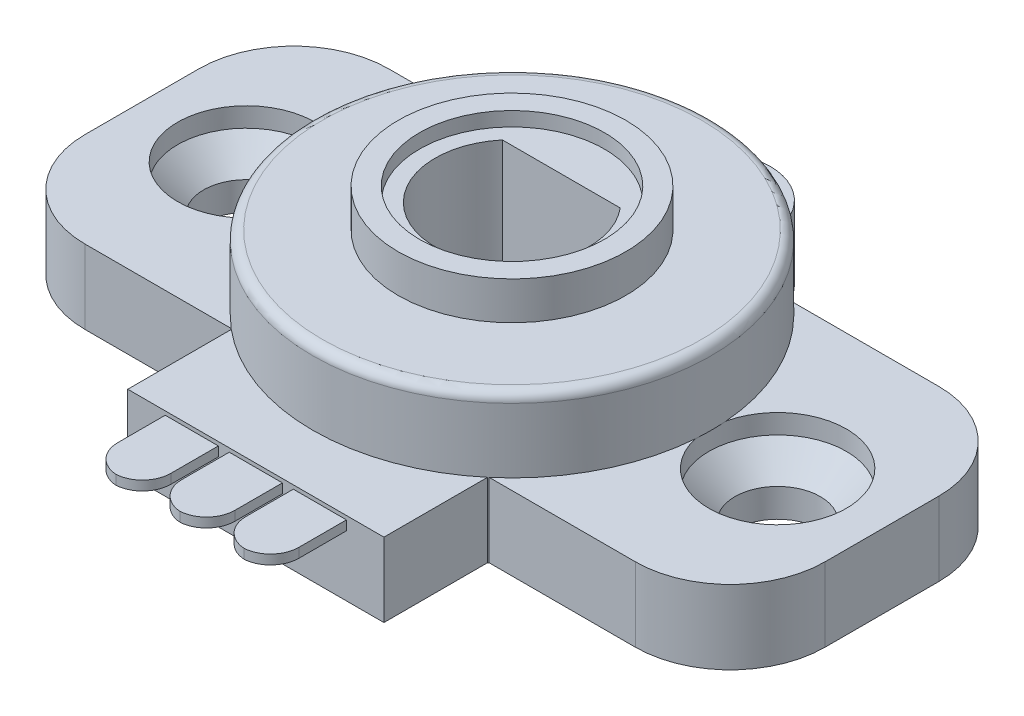
SolidWorks part; units mm, degrees
ref_plane "Front Plane" through (0, 0, 0) normal (0, 0, 1) x (1, 0, 0)
ref_plane "Top Plane" through (0, 0, 0) normal (0, 1, 0) x (1, 0, 0)
ref_plane "Right Plane" through (0, 0, 0) normal (1, 0, 0) x (0, 0, -1)
sketch "Sketch2" plane through (0, 0, 0) normal (0, 1, 0) x (1, 0, 0)
  line L0 (-1000, 0) -> (49000, 0) construction
  line L1 (-14.5, -8) -> (14.5, -8)
  line L2 (-19.5, -3) -> (-19.5, 3)
  line L3 (-14.5, 8) -> (14.5, 8)
  line L4 (19.5, -3) -> (19.5, 3)
  line L8 (-6.75, -8) -> (6.75, -8)
  line L9 (-6.75, -8) -> (-6.75, -13.5)
  line L10 (-6.75, -13.5) -> (6.75, -13.5)
  line L11 (6.75, -8) -> (6.75, -13.5)
  arc A0 (14.5, 8) -> (19.5, 3) centre (14.5, 3) cw
  arc A1 (14.5, -8) -> (19.5, -3) centre (14.5, -3) ccw
  arc A2 (-14.5, -8) -> (-19.5, -3) centre (-14.5, -3) cw
  arc A3 (-19.5, 3) -> (-14.5, 8) centre (-14.5, 3) cw
  circle A4 centre (0, 0) radius 10.5
  circle A5 centre (0, 10.5) radius 3.1
  point P0 (0, 0)
  point P1 (0, -8)
  point P2 (-19.5, 0)
  point P24 (0, -13.5)
  dimension "D3" = 5
  dimension "D4" = 21
  dimension "D5" = 6.2
  dimension "D6" = 13.6
  dimension "D1" = 39
  dimension "D2" = 16
  dimension "D7" = 13.5
  dimension "D8" = 13.5
extrude "Boss-Extrude1" add sketch "Sketch2" along normal blind 3.9 contours A4 A5 | L2 L0 A4 L3 A3 | L0 L2 A2 L1 A4 | A4 L0 L3 A5 | L0 A4 L1 | L9 A4 L11 L1 | A4 L9 L10 L11 | A4 L0 L4 A0 L3 | L0 A4 L1 A1 L4 | L3 A5 | A5 A4 L3 | L3 A5 A4 | A5 L3 A4 region at (-14.095, 0, -4.0439) region at (-14.095, 0, 4.0439) region at (0, 0, -3.7089) region at (0, 0, 3.7493) region at (14.095, 0, -4.0439) region at (14.095, 0, 4.0439) region at (-4.1241, 0, -8.7085) region at (4.1241, 0, -8.7085) region at (0, 0, -9.2649) region at (0, 0, -7.7579) region at (0, 0, -11.7298) region at (0, 0, 9.0111) region at (0, 0, 11.5437)
sketch "Sketch3" plane through (0, 3.9, 0) normal (0, 1, 0) x (1, 0, 0)
  line L0 (-1000, 0) -> (49000, 0) construction
  circle A0 centre (-14, 0) radius 2.25
  dimension "D1" = 4.5
  dimension "D2" = 14
extrude "Cut-Extrude1" cut sketch "Sketch3" against normal through all
sketch "Sketch6" plane through (0, 3.9, 0) normal (0, 1, 0) x (1, 0, 0)
  circle A0 centre (0, 0) radius 10.5
  dimension "D1" = 21
extrude "Boss-Extrude3" add sketch "Sketch6" along normal blind 7.8 from surface starting at face at (-14, 0, 2.25)
sketch "Sketch4" plane through (0, 3.9, 0) normal (0, 1, 0) x (1, 0, 0)
  circle A0 centre (-14, 0) radius 3.625
  dimension "D1" = 7.25
extrude "Cut-Extrude2" cut sketch "Sketch4" against normal blind 2.4
sketch "Sketch5" plane through (0, 0, 0) normal (0, 0, 1) x (1, 0, 0)
  line L0 (-14, -999.2025) -> (-14, 49000.7975) construction
  line L1 (-16.25, 1.5) -> (-17.625, 2.875)
  line L2 (-17.625, 2.875) -> (-17.625, 1.5)
  line L3 (-17.625, 1.5) -> (-16.25, 1.5)
  dimension "D1" = 14
  dimension "D2" = 45
  dimension "D3" = 4.5
  dimension "D4" = 7.25
  dimension "D5" = 1.5
revolve "Revolve1" add sketch "Sketch5" angle 360 about L0
mirror "Mirror1" about plane through (0, 0, 0) normal (1, 0, 0) of "Cut-Extrude1", "Cut-Extrude2", "Revolve1"
sketch "Sketch7" plane through (0, 7.8, 0) normal (0, 1, 0) x (1, 0, 0)
  circle A0 centre (0, 0) radius 6
  dimension "D1" = 12
extrude "Boss-Extrude4" add sketch "Sketch7" along normal blind 9.8 from surface starting at face at (14, 0, 2.25)
sketch "Sketch8" plane through (0, 9.8, 0) normal (0, 1, 0) x (1, 0, 0)
  circle A0 centre (0, 0) radius 4.875
  dimension "D1" = 9.75
extrude "Cut-Extrude3" cut sketch "Sketch8" against normal blind 0.75
sketch "Sketch9" plane through (0, 9.05, 0) normal (0, 1, 0) x (1, 0, 0)
  line L0 (-3.1052, 2.6) -> (3.1052, 2.6)
  arc A0 (3.1052, 2.6) -> (-3.1052, 2.6) centre (0, 0) ccw construction
  arc A1 (-3.1052, 2.6) -> (3.1052, 2.6) centre (0, 0) ccw
  point P1 (0, -4.05)
  dimension "D1" = 8.1
  dimension "D2" = 6.65
extrude "Cut-Extrude4" cut sketch "Sketch9" against normal through all
sketch "Sketch10" plane through (0, 0, 0) normal (0, -1, 0) x (1, 0, 0)
  circle A0 centre (0, 0) radius 6
  dimension "D1" = 12
extrude "Cut-Extrude5" cut sketch "Sketch10" against normal blind 1.75
sketch "Sketch11" plane through (0, 0, 0) normal (0, 1, 0) x (1, 0, 0)
  line L0 (-6.75, -13.5) -> (6.75, -13.5) construction
  line L1 (-4.775, -13.5) -> (-1.975, -13.5)
  line L2 (-4.775, -13.5) -> (-4.775, -17.5)
  line L3 (-4.775, -17.5) -> (-1.975, -17.5)
  line L4 (-1.975, -13.5) -> (-1.975, -17.5)
  line L5 (-6.75, -8.0429) -> (-6.75, -13.5) construction
  line L6 (-1.4, -13.5) -> (1.4, -13.5)
  line L7 (-1.4, -13.5) -> (-1.4, -17.5)
  line L8 (-1.4, -17.5) -> (1.4, -17.5)
  line L9 (1.4, -13.5) -> (1.4, -17.5)
  line L10 (1.975, -13.5) -> (4.775, -13.5)
  line L11 (1.975, -13.5) -> (1.975, -17.5)
  line L12 (1.975, -17.5) -> (4.775, -17.5)
  line L13 (4.775, -13.5) -> (4.775, -17.5)
  line L14 (6.75, -8.0429) -> (6.75, -13.5) construction
  point P18 (-3.375, -17.5)
  point P21 (3.375, -17.5)
  point P22 (0, -17.5)
  dimension "D1" = 2.8
  dimension "D2" = 2.8
  dimension "D3" = 2.8
  dimension "D4" = 17.5
  dimension "D5" = 3.375
  dimension "D6" = 3.375
  dimension "D7" = 6.75
extrude "Boss-Extrude5" add sketch "Sketch11" along normal blind 0.5 from offset 3.2
fillet "Fillet1" radius 1.5 6 edges at (-4.775, 3.45, 17.5) (-1.975, 3.45, 17.5) (-1.4, 3.45, 17.5) (1.4, 3.45, 17.5) (1.975, 3.45, 17.5) (4.775, 3.45, 17.5)
fillet "Fillet2" radius 0.5 1 edges at (0, 7.8, 10.5)
